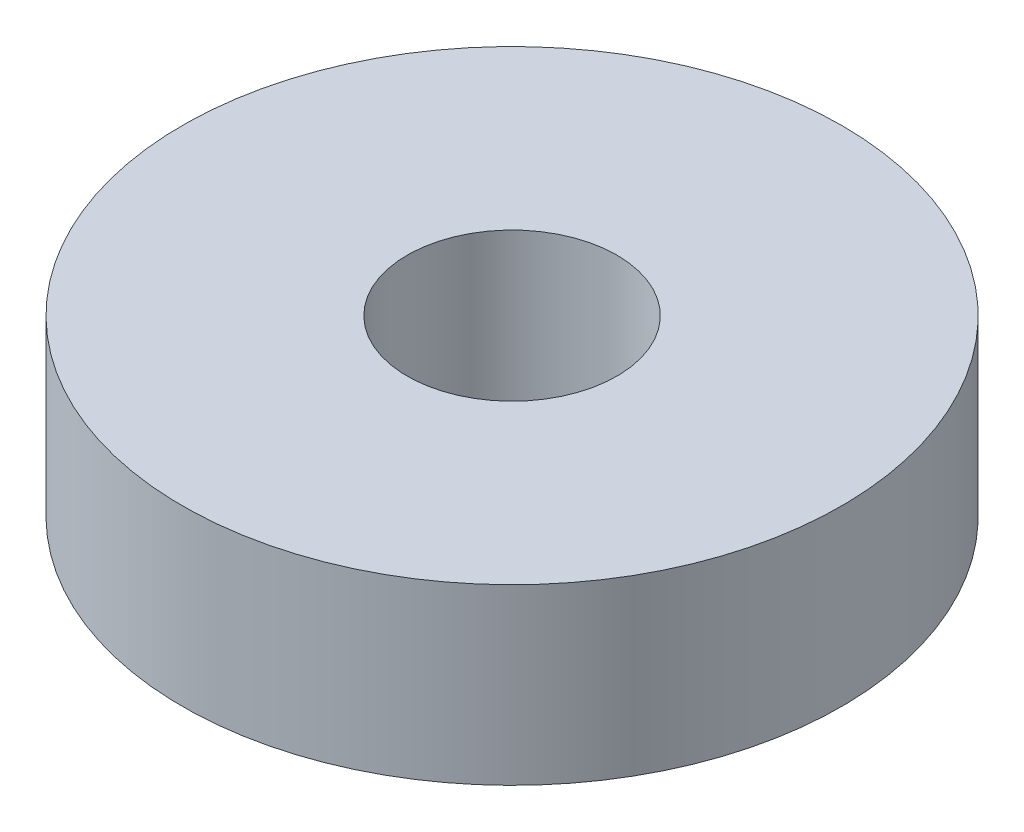
SolidWorks part; units mm, degrees
ref_plane "Front Plane" through (0, 0, 0) normal (0, 0, 1) x (1, 0, 0)
ref_plane "Top Plane" through (0, 0, 0) normal (0, 1, 0) x (1, 0, 0)
ref_plane "Right Plane" through (0, 0, 0) normal (1, 0, 0) x (0, 0, -1)
sketch "Sketch1" plane through (0, 0, 0) normal (0, 1, 0) x (1, 0, 0)
  circle A0 centre (0, 0) radius 55
  dimension "FLANGE_OD" = 110
extrude "Boss-Extrude1" add sketch "Sketch1" along normal blind 29
sketch "Sketch2" plane through (0, 0, 0) normal (0, 1, 0) x (1, 0, 0)
  circle A0 centre (0, 0) radius 17.5
  dimension "BORE_D" = 35
extrude "Cut-Extrude1" cut sketch "Sketch2" along normal through all
sketch "Sketch3" plane through (0, 29, 0) normal (0, 1, 0) x (1, 0, 0)
  circle A0 centre (0, 0) radius 12.0949 construction
  circle A1 centre (-12.0949, 0) radius 2.2381
  dimension "BOLT_D" = 4.4763
  dimension "BOLT_PCD" = 24.1898
extrude "Cut-Extrude2" cut sketch "Sketch3" against normal blind 24.0281 rebuild error yes
pattern_circular "CirPattern1" count 3 over 360 rebuild error yes
